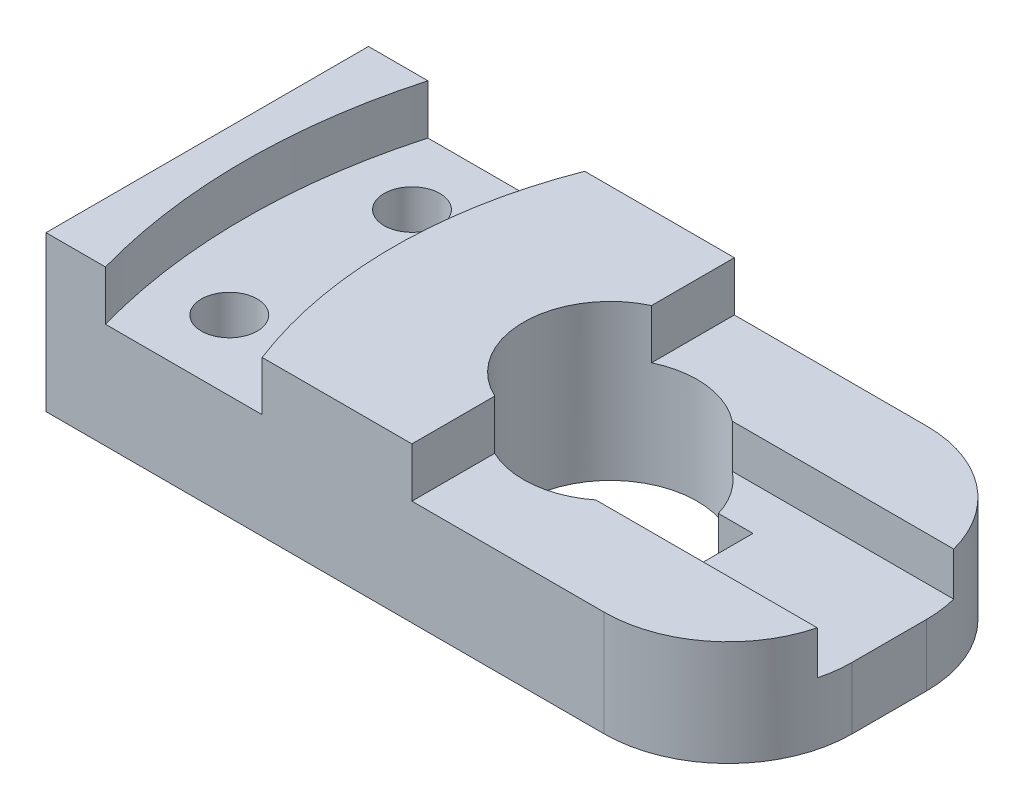
SolidWorks part; units mm, degrees
ref_plane "Front Plane" through (0, 0, 0) normal (0, 0, 1) x (1, 0, 0)
ref_plane "Top Plane" through (0, 0, 0) normal (0, 1, 0) x (1, 0, 0)
ref_plane "Right Plane" through (0, 0, 0) normal (1, 0, 0) x (0, 0, -1)
sketch "Sketch1" plane through (0, 0, 0) normal (0, 1, 0) x (1, 0, 0)
  line L0 (0, 26) -> (0, -26)
  line L1 (0, -26) -> (90, -26)
  line L2 (0, 26) -> (90, 26)
  line L3 (-12.3636, 0) -> (87.765, 0) construction
  line L4 (110, -6) -> (110, 6)
  line L5 (65, 0) -> (-5.7043, 22.293) construction
  line L6 (65, 0) -> (-4.7221, -21.9833) construction
  line L7 (78.4164, 4) -> (84, 4)
  line L8 (78.4164, -4) -> (84, -4)
  line L9 (84, 4) -> (84, -4)
  line L10 (59, 26) -> (59, 12.6491)
  line L11 (73.6603, 11) -> (110, 11)
  line L12 (73.6603, -11) -> (110, -11)
  line L13 (59, -12.6491) -> (59, -26)
  arc A1 (34.8584, 26) -> (34.8584, -26) centre (102, 0) ccw
  arc A2 (21.0741, 26) -> (21.0741, -26) centre (102, 0) ccw construction
  arc A3 (9.5879, 26) -> (9.5879, -26) centre (102, 0) ccw
  circle A4 centre (18.2858, 14.7289) radius 4.5
  circle A5 centre (18.2858, -14.7289) radius 4.5
  arc A6 (78.4164, 4) -> (78.4164, -4) centre (65, 0) ccw
  arc A7 (90, -26) -> (110, -6) centre (90, -6) ccw
  arc A8 (110, 6) -> (90, 26) centre (90, 6) ccw
  point P5 (102, 0)
  point P32 (74.3869, -10.3869)
  point P33 (74.1164, 10.625)
  point P34 (110, 10.625)
  point P35 (110, -10.5577)
  point P36 (87.765, 0)
  point P41 (110, -26)
  dimension "D4" = 192
  dimension "D5" = 170
  dimension "D6" = 144
  dimension "D10" = 9
  dimension "D11" = 9
  dimension "D12" = 28
  dimension "D17" = 20
  dimension "D1" = 8
  dimension "D2" = 110
  dimension "D3" = 52
  dimension "D7" = 45
  dimension "D8" = 35
  dimension "D9" = 17.5
  dimension "D13" = 8
  dimension "D14" = 19
  dimension "D15" = 22
  dimension "D16" = 51
extrude "Boss-Extrude1" add sketch "Sketch1" along normal blind 17 contours L11 A8 L2 L10 A6 | L1 A7 L12 A6 L13 | L2 A3 L1 A1 A5 A4 region at (19.5365, 0, 0) region at (82.7226, 0, -18.4026) region at (82.7226, 0, 18.4026)
extrude "Boss-Extrude2" add sketch "Sketch1<3>" along normal blind 25 contours A6 L10 L2 A1 L1 L13 | A3 L2 L0 L1 region at (3.6726, 0, 0) region at (44.0757, 0, 0)
sketch "Sketch1<3>" plane through (0, 0, 0) normal (0, 1, 0) x (1, 0, 0) same geometry as "Sketch1"
extrude "Boss-Extrude3" add sketch "Sketch1<4>" along normal blind 10 contours L4 A8 L11 A6 L7 L9 L8 L12 A7 region at (94.3605, 0, 0)
sketch "Sketch1<4>" plane through (0, 0, 0) normal (0, 1, 0) x (1, 0, 0) same geometry as "Sketch1"
